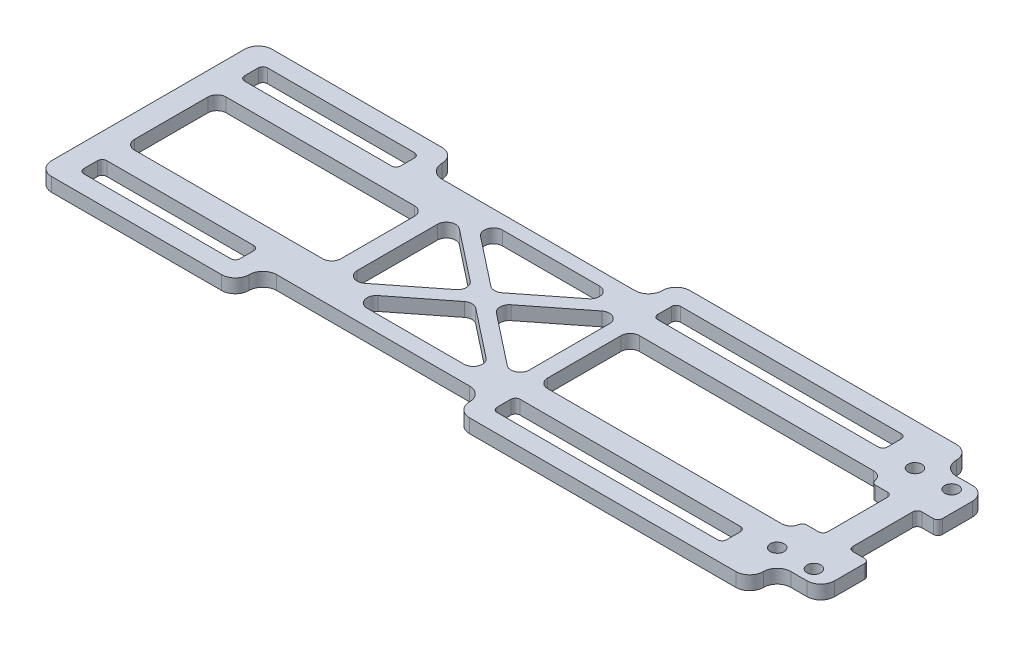
SolidWorks part; units mm, degrees
material "碳纤维"
ref_plane "前视基准面" through (0, 0, 0) normal (0, 0, 1) x (1, 0, 0)
ref_plane "上视基准面" through (0, 0, 0) normal (0, 1, 0) x (1, 0, 0)
ref_plane "右视基准面" through (0, 0, 0) normal (1, 0, 0) x (0, 0, -1)
sketch "草图1" plane through (0, 0, 0) normal (0, 1, 0) x (1, 0, 0)
  line L0 (-72.5, -15) -> (-38.5, -15)
  line L1 (-77.5, -24) -> (77.5, -24)
  line L2 (-77.5, -24) -> (-77.5, 24)
  line L3 (-77.5, 24) -> (77.5, 24)
  line L4 (77.5, -24) -> (77.5, 24)
  line L5 (0, 24) -> (0, -24) construction
  line L6 (-77.5, 0) -> (77.5, 0) construction
  line L7 (-27.5, 10) -> (-72.5, 10)
  line L8 (-27.5, 10) -> (-27.5, -10)
  line L9 (-27.5, -10) -> (-72.5, -10)
  line L10 (-72.5, 10) -> (-72.5, -10)
  line L11 (-50, -10) -> (-50, 10) construction
  line L12 (-27.5, 0) -> (-72.5, 0) construction
  line L13 (-72.5, 20) -> (-38.5, 20)
  line L14 (-72.5, 20) -> (-72.5, 15)
  line L15 (-72.5, 15) -> (-38.5, 15)
  line L16 (-38.5, 20) -> (-38.5, 15)
  line L17 (-55.5, 15) -> (-55.5, 20) construction
  line L18 (-72.5, 17.5) -> (-38.5, 17.5) construction
  line L19 (-38.5, -20) -> (-38.5, -15)
  line L20 (-72.5, -20) -> (-38.5, -20)
  line L21 (-72.5, -20) -> (-72.5, -15)
  line L23 (17.5, 10) -> (72.5, 10)
  line L24 (17.5, 10) -> (17.5, -10)
  line L25 (17.5, -10) -> (72.5, -10)
  line L26 (72.5, 10) -> (72.5, -10)
  line L27 (45, -10) -> (45, 10) construction
  line L28 (17.5, 0) -> (72.5, 0) construction
  line L29 (17.5, -15) -> (67.5, -15)
  line L30 (17.5, -15) -> (17.5, -20)
  line L31 (17.5, -20) -> (67.5, -20)
  line L32 (67.5, -15) -> (67.5, -20)
  line L33 (42.5, -20) -> (42.5, -15) construction
  line L34 (17.5, -17.5) -> (67.5, -17.5) construction
  line L35 (17.5, 20) -> (67.5, 20)
  line L36 (17.5, 20) -> (17.5, 15)
  line L37 (17.5, 15) -> (67.5, 15)
  line L38 (67.5, 20) -> (67.5, 15)
  line L39 (42.5, 15) -> (42.5, 20) construction
  line L40 (17.5, 17.5) -> (67.5, 17.5) construction
  circle A0 centre (74.5, 15) radius 1.5
  circle A1 centre (74.5, -15) radius 1.5
  point P0 (0, 0)
  point P110 (45, 0)
  point P126 (-50, 0)
  point P132 (42.5, -17.5)
  point P145 (42.5, 17.5)
  point P157 (-55.5, 17.5)
  dimension "D13" = 3
  dimension "D1" = 155
  dimension "D2" = 48
  dimension "D3" = 5
  dimension "D4" = 45
  dimension "D5" = 34
  dimension "D6" = 5
  dimension "D7" = 5
  dimension "D8" = 20
  dimension "D9" = 55
  dimension "D10" = 50
  dimension "D11" = 45
  dimension "D12" = 7
  dimension "D14" = 30
extrude "凸台-拉伸1" add sketch "草图1" along normal blind 3
sketch "草图3" plane through (0, 3, 0) normal (0, 1, 0) x (1, 0, 0)
  line L0 (77.5, -24) -> (77.5, 24) construction
  line L1 (77.5, 18) -> (87, 18)
  line L2 (77.5, 18) -> (77.5, -18)
  line L3 (77.5, -18) -> (87, -18)
  line L4 (87, 18) -> (87, -18)
  line L5 (82.25, -18) -> (82.25, 18) construction
  line L6 (77.5, 0) -> (87, 0) construction
  line L7 (78.5, 18) -> (78.5, -18) construction
  circle A0 centre (74.5, -15) radius 1.5 construction
  circle A1 centre (74.5, 15) radius 1.5 construction
  circle A2 centre (74.5, -15) radius 1.5 construction
  circle A3 centre (74.5, 15) radius 1.5 construction
  circle A4 centre (82.5, -15) radius 1.5
  circle A5 centre (82.5, 15) radius 1.5
  point P224 (82.25, 0)
  dimension "D1" = 9.5
  dimension "D2" = 36
  dimension "D3" = 8
extrude "凸台-拉伸3" add sketch "草图3" against normal up to surface (3 mm away) up to face at (74.5, 0, 13.5)
fillet "圆角4" radius 1 16 edges at (17.5, 1.5, 20) (67.5, 1.5, 20) (17.5, 1.5, 15) (67.5, 1.5, 15) (17.5, 1.5, -15) (67.5, 1.5, -15) (17.5, 1.5, -20) (67.5, 1.5, -20) (-72.5, 1.5, 20) (-38.5, 1.5, 20) (-72.5, 1.5, 15) (-38.5, 1.5, 15) (-72.5, 1.5, -15) (-38.5, 1.5, -15) (-72.5, 1.5, -20) (-38.5, 1.5, -20)
fillet "圆角5" radius 2 8 edges at (-72.5, 1.5, -10) (-72.5, 1.5, 10) (-27.5, 1.5, 10) (-27.5, 1.5, -10) (17.5, 1.5, 10) (72.5, 1.5, 10) (17.5, 1.5, -10) (72.5, 1.5, -10)
sketch "草图4" plane through (0, 3, 0) normal (0, 1, 0) x (1, 0, 0)
  line L1 (14, -14.5) -> (-23.5, -14.5) construction
  line L2 (14, -14.5) -> (14, 15) construction
  line L3 (14, 15) -> (-23.5, 15) construction
  line L4 (-23.5, -14.5) -> (-23.5, 15) construction
  line L5 (-4.75, 15) -> (-4.75, -14.5) construction
  line L6 (14, 0.25) -> (-23.5, 0.25) construction
  line L9 (17.5, 8) -> (17.5, -8) construction
  line L10 (-27.5, -8) -> (-27.5, 8) construction
  line L11 (-23.5, 15) -> (-4.75, 0.25) construction
  line L12 (-21.0739, 15) -> (-4.75, 2.1585)
  line L13 (-4.75, 2.1585) -> (11.5739, 15)
  line L14 (11.5739, 15) -> (-21.0739, 15)
  line L15 (-23.5, 13.0915) -> (-23.5, -12.5915)
  line L16 (-23.5, -12.5915) -> (-7.1761, 0.25)
  line L17 (-7.1761, 0.25) -> (-23.5, 13.0915)
  line L18 (-4.75, -1.6585) -> (11.5739, -14.5)
  line L19 (-21.0739, -14.5) -> (-4.75, -1.6585)
  line L20 (11.5739, -14.5) -> (-21.0739, -14.5)
  line L21 (14, -12.5915) -> (-2.3239, 0.25)
  line L22 (14, 13.0915) -> (14, -12.5915)
  line L23 (-2.3239, 0.25) -> (14, 13.0915)
  line L25 (77.5, 24) -> (-77.5, 24) construction
  line L26 (-34.5, 24) -> (13.5, 24)
  line L27 (-34.5, 24) -> (-34.5, 18)
  line L28 (-34.5, 18) -> (13.5, 18)
  line L29 (13.5, 24) -> (13.5, 18)
  line L30 (-10.5, 18) -> (-10.5, 24) construction
  line L31 (-34.5, 21) -> (13.5, 21) construction
  line L32 (-77.5, -24) -> (77.5, -24) construction
  line L33 (-34.5, -24) -> (13.5, -24)
  line L34 (-34.5, -24) -> (-34.5, -18)
  line L35 (-34.5, -18) -> (13.5, -18)
  line L36 (13.5, -24) -> (13.5, -18)
  line L37 (-10.5, -18) -> (-10.5, -24) construction
  line L38 (-34.5, -21) -> (13.5, -21) construction
  line L42 (17.5, 19) -> (17.5, 16) construction
  line L43 (-38.5, 16) -> (-38.5, 19) construction
  line L44 (17.5, -16) -> (17.5, -19) construction
  line L45 (-38.5, -19) -> (-38.5, -16) construction
  point P18 (-12.912, 8.5793)
  point P220 (-10.5, -21)
  point P244 (-4.75, 0.25)
  point P255 (-10.5, 21)
  dimension "D1" = 3.5
  dimension "D2" = 4
  dimension "D3" = 3
  dimension "D4" = 6
  dimension "D5" = 6
  dimension "D6" = 3
  dimension "D7" = 3.5
  dimension "D8" = 4
  dimension "D9" = 4
  dimension "D10" = 4
  dimension "D11" = 4
extrude "切除-拉伸1" cut sketch "草图4" against normal through all
fillet "圆角3" radius 2 12 edges at (11.5739, 1.5, -15) (-4.75, 1.5, -2.1585) (-21.0739, 1.5, -15) (14, 1.5, 12.5915) (-2.3239, 1.5, -0.25) (-7.1761, 1.5, -0.25) (-23.5, 1.5, 12.5915) (-23.5, 1.5, -13.0915) (-4.75, 1.5, 1.6585) (11.5739, 1.5, 14.5) (-21.0739, 1.5, 14.5) (14, 1.5, -13.0915)
fillet "圆角1" radius 3 16 edges at (77.5, 1.5, 24) (-77.5, 1.5, 24) (77.5, 1.5, -24) (77.5, 1.5, -18) (87, 1.5, -18) (87, 1.5, 18) (77.5, 1.5, 18) (-77.5, 1.5, -24) (-34.5, 1.5, 18) (13.5, 1.5, 18) (13.5, 1.5, 24) (13.5, 1.5, -24) (13.5, 1.5, -18) (-34.5, 1.5, -18) (-34.5, 1.5, 24) (-34.5, 1.5, -24)
sketch "草图5" plane through (0, 3, 0) normal (0, 1, 0) x (1, 0, 0)
  line L0 (72.5, 0) -> (87, 0) construction
  line L1 (72.5, -8) -> (72.5, 8) construction
  line L2 (87, -15) -> (87, 15) construction
  line L17 (82.5, -7.5) -> (87, -7.5)
  line L22 (82.5, -7.5) -> (82.5, 7.5)
  line L23 (82.5, 7.5) -> (87, 7.5)
  line L31 (87, -7.5) -> (87, 7.5)
  line L32 (77, 7.5) -> (72.5, 7.5)
  line L33 (77, 7.5) -> (77, -7.5)
  line L34 (77, -7.5) -> (72.5, -7.5)
  line L35 (72.5, 7.5) -> (72.5, -7.5)
  line L36 (74.75, -7.5) -> (74.75, 7.5) construction
  line L37 (77, 0) -> (72.5, 0) construction
  line L38 (84.75, 7.5) -> (84.75, -7.5) construction
  line L39 (82.5, 0) -> (87, 0) construction
  point P120 (84.75, 0)
  point P173 (74.75, 0)
  dimension "D1" = 15
  dimension "D2" = 4.5
  dimension "D3" = 4.5
  dimension "D4" = 5.5
extrude "切除-拉伸2" cut sketch "草图5" against normal through all
fillet "圆角6" radius 1 8 edges at (82.5, 1.5, 7.5) (82.5, 1.5, -7.5) (87, 1.5, 7.5) (87, 1.5, -7.5) (77, 1.5, -7.5) (77, 1.5, 7.5) (72.5, 1.5, 7.5) (72.5, 1.5, -7.5)
move or copy body "实体-移动/复制1" [suppressed] bodies to move or copy 110
